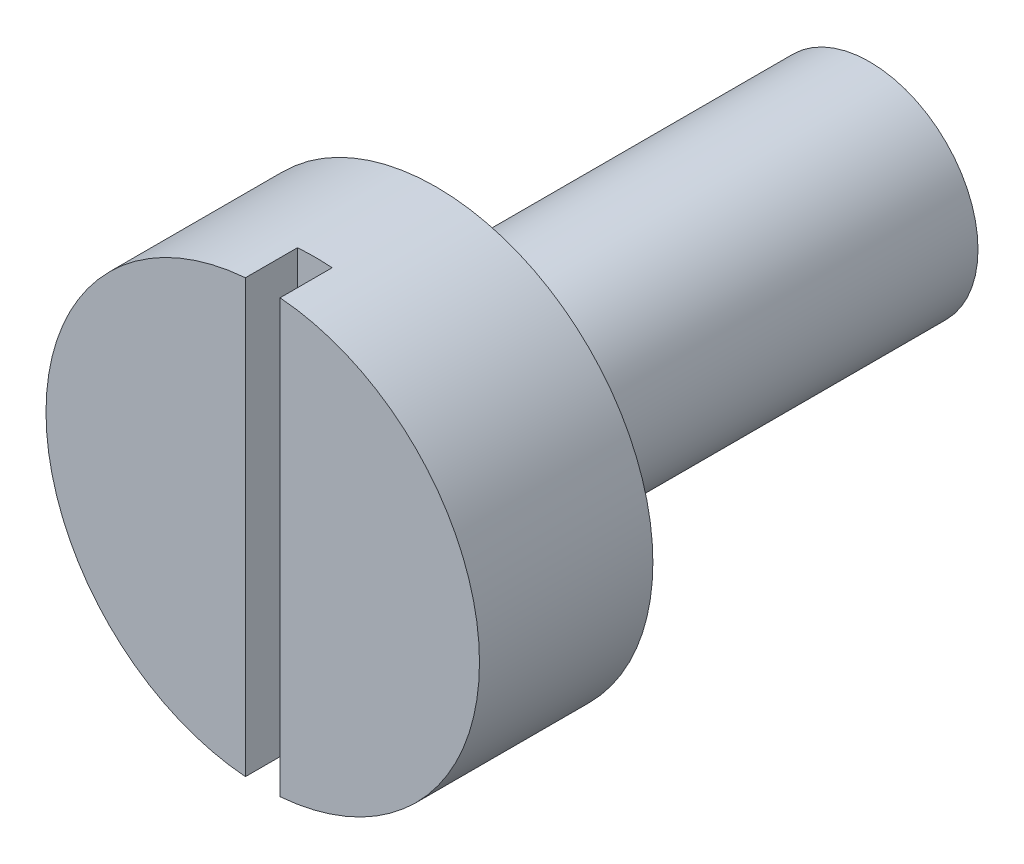
SolidWorks part; units mm, degrees
ref_plane "Спереди" through (0, 0, 0) normal (0, 0, 1) x (1, 0, 0)
ref_plane "Сверху" through (0, 0, 0) normal (0, 1, 0) x (1, 0, 0)
ref_plane "Справа" through (0, 0, 0) normal (1, 0, 0) x (0, 0, -1)
sketch "Эскиз1" plane through (0, 0, 0) normal (0, 0, 1) x (1, 0, 0)
  circle A0 centre (0, 0) radius 2.5
  dimension "D1" = 5
extrude "Вытянуть1" add sketch "Эскиз1" along normal blind 5 and the other way blind 5
sketch "Эскиз2" plane through (0, 0, 5) normal (0, 0, 1) x (1, 0, 0)
  circle A0 centre (0, 0) radius 5
  dimension "D1" = 10
extrude "Вытянуть2" add sketch "Эскиз2" along normal blind 4
sketch "Эскиз3" plane through (0, 0, 9) normal (0, 0, 1) x (1, 0, 0)
  line L0 (0, 1.8714) -> (0, -1.7382) construction
  line L1 (-0.4, -5.4661) -> (0.4, -5.4661)
  line L2 (-0.4, -5.4661) -> (-0.4, 5.5549)
  line L3 (-0.4, 5.5549) -> (0.4, 5.5549)
  line L4 (0.4, -5.4661) -> (0.4, 5.5549)
  dimension "D1" = 0.8
extrude "Вырез-Вытянуть1" cut sketch "Эскиз3" against normal blind 1.2
